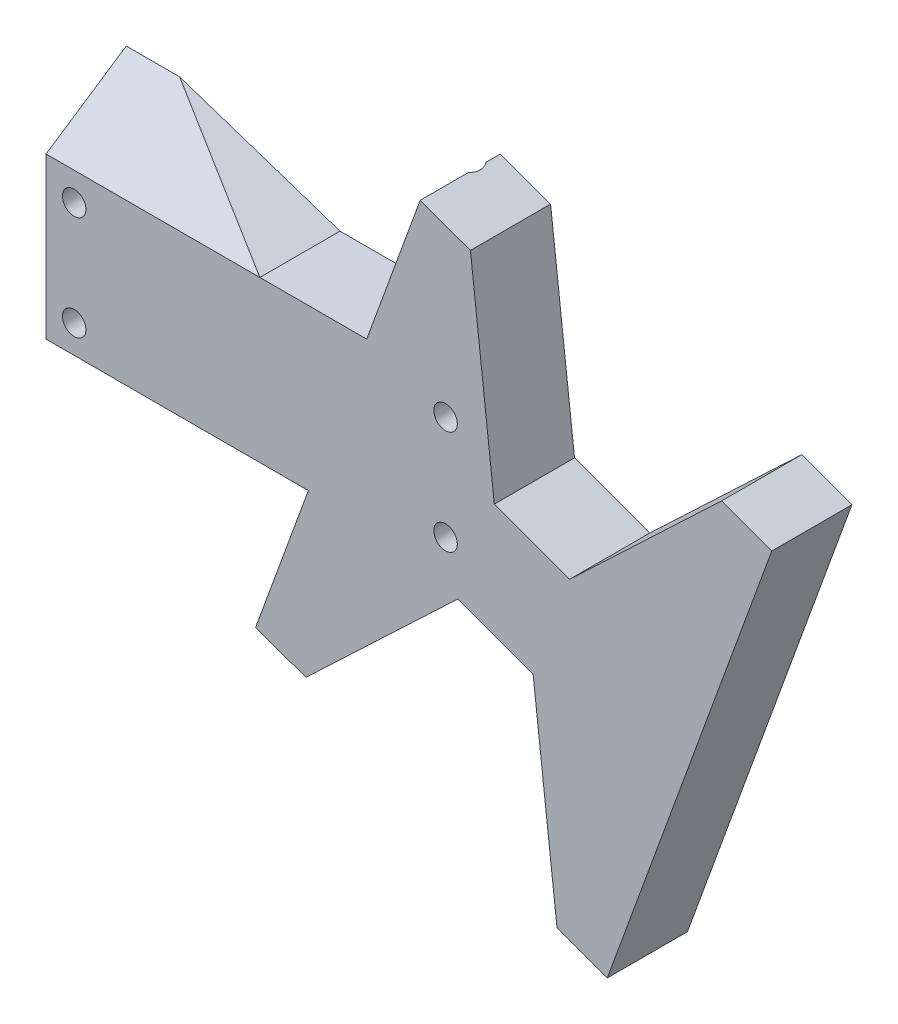
SolidWorks part; units mm, degrees
ref_plane "Front Plane" through (0, 0, 0) normal (0, 0, 1) x (1, 0, 0)
ref_plane "Top Plane" through (0, 0, 0) normal (0, 1, 0) x (1, 0, 0)
ref_plane "Right Plane" through (0, 0, 0) normal (1, 0, 0) x (0, 0, -1)
sketch "Sketch1" plane through (0, 0, 0) normal (0, 0, 1) x (1, 0, 0)
  line L1 (-25.4, 9.525) -> (25.4, 9.525)
  line L2 (-25.4, 9.525) -> (-25.4, -9.525)
  line L3 (-25.4, -9.525) -> (25.4, -9.525)
  line L4 (25.4, 9.525) -> (25.4, -9.525)
  line L5 (-25.4, 9.525) -> (25.4, -9.525) construction
  line L6 (-25.4, -9.525) -> (25.4, 9.525) construction
  point P0 (0, 0)
  dimension "D1" = 50.8
  dimension "D2" = 19.05
extrude "Boss-Extrude1" add sketch "Sketch1" along normal blind 9.525
sketch "Sketch11" plane through (0, 0, 9.525) normal (0, 0, 1) x (1, 0, 0)
  line L0 (19.05, 26.9875) -> (-0.4965, -26.7159)
  line L1 (-0.4965, -26.7159) -> (41.2729, -41.9187)
  line L2 (41.2729, -41.9187) -> (60.8193, 11.7847)
  line L3 (60.8193, 11.7847) -> (19.05, 26.9875)
  line L4 (-25.4, -9.525) -> (25.4, -9.525) construction
  dimension "D1" = 57.15
  dimension "D2" = 44.45
  dimension "D3" = 70
  dimension "D4" = 19.05
  dimension "D5" = 26.9875
extrude "Boss-Extrude4" add sketch "Sketch11" against normal up to surface (9.525 mm away) up to face at (0, 0, 0)
sketch "Sketch12" plane through (0, 0, 9.525) normal (0, 0, 1) x (1, 0, 0)
  line L0 (25.017, 24.8157) -> (27.858, 0.1303)
  line L1 (60.8193, 11.7847) -> (19.05, 26.9875) construction
  line L3 (54.8523, 13.9565) -> (25.017, 24.8157)
  line L4 (51.0461, -15.067) -> (11.0348, -0.5041) construction
  line L5 (41.2729, -41.9187) -> (60.8193, 11.7847) construction
  line L13 (27.858, 0.1303) -> (36.8086, -3.1274)
  line L14 (36.8086, -3.1274) -> (54.8523, 13.9565)
  line L15 (35.3058, -39.7469) -> (5.4706, -28.8878)
  line L16 (5.4706, -28.8878) -> (23.5143, -11.8038)
  line L17 (23.5143, -11.8038) -> (32.4649, -15.0615)
  line L18 (32.4649, -15.0615) -> (35.3058, -39.7469)
  dimension "D1" = 6.35
  dimension "D2" = 6.35
  dimension "D3" = 9.525
  dimension "D4" = 6.35
extrude "Cut-Extrude5" cut sketch "Sketch12" against normal through all
sketch "Sketch2" plane through (0, 0, 9.525) normal (0, 0, 1) x (1, 0, 0)
  line L0 (-22.0599, 6.1849) -> (-22.0599, -6.1849) construction
  line L1 (-22.0599, 6.1849) -> (-25.4, 6.1849) construction
  line L2 (-25.4, 9.525) -> (-25.4, -9.525) construction
  line L3 (-22.0599, 6.1849) -> (-22.0599, 9.525) construction
  line L4 (12.6942, 9.525) -> (-25.4, 9.525) construction
  line L5 (0, -9.525) -> (0, 9.525) construction
  line L6 (12.6942, 9.525) -> (-25.4, 9.525) construction
  line L7 (-25.4, -9.525) -> (5.7605, -9.525) construction
  circle A0 centre (-22.0599, 6.1849) radius 1.397
  circle A1 centre (-22.0599, -6.1849) radius 1.397
  circle A2 centre (22.0599, -6.1849) radius 1.397
  circle A3 centre (22.0599, 6.1849) radius 1.397
  point P4 (-22.0599, 0)
  point P15 (0, 0)
  dimension "D1" = 12.3698
  dimension "D2" = 2.794
  dimension "D3" = 2.794
  dimension "D4" = 25.4
extrude "Cut-Extrude1" cut sketch "Sketch2" against normal through all
sketch "Sketch4" plane through (0, 9.525, 0) normal (0, 1, 0) x (1, 0, 0)
  line L1 (0, 0) -> (0, -9.525) construction
  line L2 (12.6942, -9.525) -> (-25.4, -9.525) construction
  line L3 (-25.4, -9.525) -> (-25.4, 0) construction
  circle A2 centre (-17.4625, -2.7305) radius 1.905
  circle A3 centre (17.4625, -2.7305) radius 1.905
  dimension "D1" = 25.4
  dimension "D4" = 3.81
  dimension "D2" = 7.9375
  dimension "D3" = 6.7945
extrude "Cut-Extrude2" cut sketch "Sketch4" against normal through all both and the other way through all
sketch "Sketch5" plane through (0, 9.525, 0) normal (0, 1, 0) x (1, 0, 0)
  line L0 (14.2875, -2.7305) -> (14.2875, 0)
  line L1 (12.6942, 0) -> (-25.4, 0) construction
  line L2 (20.6375, -2.7305) -> (20.6375, 0)
  line L3 (14.2875, 0) -> (20.6375, 0)
  arc A1 (14.2875, -2.7305) -> (20.6375, -2.7305) centre (17.4625, -2.7305) ccw
  arc A2 (19.05, -1.6775) -> (19.05, -3.7835) centre (17.4625, -2.7305) ccw construction
  dimension "D1" = 3.175
extrude "Cut-Extrude3" cut sketch "Sketch5" against normal blind 3.175 from offset 9.525 offset against normal yes
sketch "Sketch6" plane through (0, 9.525, 0) normal (0, 1, 0) x (1, 0, 0)
  line L0 (-14.2875, -2.7305) -> (-14.2875, 0)
  line L1 (12.6942, 0) -> (-25.4, 0) construction
  line L2 (-20.6375, -2.7305) -> (-20.6375, 0)
  line L3 (-20.6375, 0) -> (-14.2875, 0)
  arc A0 (-20.6375, -2.7305) -> (-14.2875, -2.7305) centre (-17.4625, -2.7305) ccw
  dimension "D1" = 6.35
extrude "Cut-Extrude4" cut sketch "Sketch6" against normal blind 3.175 from offset 6.35 offset against normal yes
sketch "Sketch9" plane through (0, 0, 0) normal (0, 0, -1) x (-1, 0, 0)
  circle A0 centre (-22.0599, 6.1849) radius 1.397
  circle A1 centre (-22.0599, 6.1849) radius 2.6987
  circle A2 centre (-22.0599, 6.1849) radius 1.397 construction
  circle A3 centre (22.0599, -6.1849) radius 1.397
  circle A4 centre (22.0599, -6.1849) radius 2.6987
  circle A5 centre (22.0599, -6.1849) radius 1.397 construction
  dimension "D1" = 5.3975
  dimension "D2" = 5.3975
extrude "Boss-Extrude2" add sketch "Sketch9" along normal blind 2.667
chamfer "Chamfer1" distance 0.635 angle 45 2 edges at (-24.7586, -6.1849, -2.667) (19.3611, 6.1849, -2.667)
sketch "Sketch13" plane through (0, 9.525, 0) normal (0, 1, 0) x (1, 0, 0)
  line L0 (12.6942, -9.525) -> (-25.4, -9.525) construction
  line L1 (-25.4, 0) -> (0, 0)
  line L2 (-25.4, 0) -> (-25.4, -9.525)
  line L3 (-25.4, -9.525) -> (0, -9.525)
  line L4 (0, 0) -> (0, -9.525)
  dimension "D1" = 25.4
extrude "Boss-Extrude5" add sketch "Sketch13" along normal blind 6.35
chamfer "Chamfer3" distance 6.35 distance2 19.05 1 edges at (0, 15.875, 4.7625) first distance on face at (0, 12.7, 4.7625)
chamfer "Chamfer2" distance 6.35 distance2 9.525 1 edges at (-22.225, 15.875, 9.525) first distance on face at (20.6629, 6.1849, 9.525)
